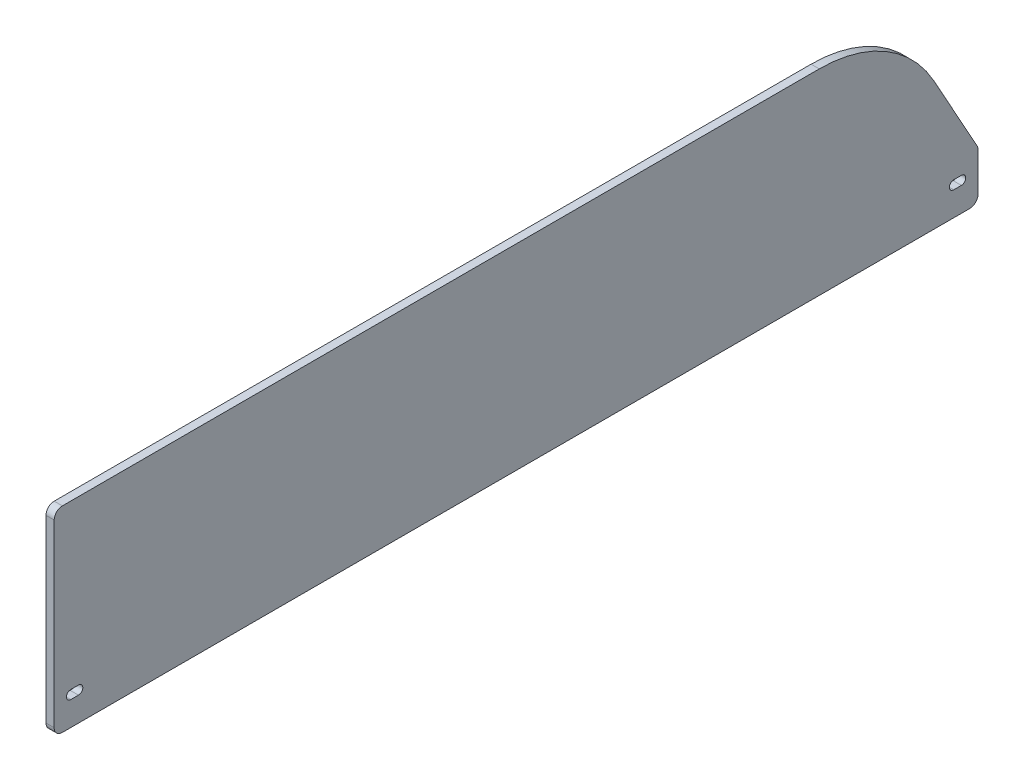
SolidWorks part; units mm, degrees
material "ABS PC"
ref_plane "Front Plane" through (0, 0, 0) normal (0, 0, 1) x (1, 0, 0)
ref_plane "Top Plane" through (0, 0, 0) normal (0, 1, 0) x (1, 0, 0)
ref_plane "Right Plane" through (0, 0, 0) normal (1, 0, 0) x (0, 0, -1)
sketch "Sketch1" plane through (0, 0, 0) normal (1, 0, 0) x (0, 0, -1)
  line L0 (0, 0) -> (0, 152.4)
  line L1 (0, 152.4) -> (654.05, 152.4)
  line L2 (654.05, 152.4) -> (717.55, 38.1)
  line L3 (717.55, 38.1) -> (717.55, 0)
  line L4 (717.55, 0) -> (0, 0)
  dimension "D1" = 38.1
  dimension "D2" = 717.55
  dimension "D3" = 152.4
  dimension "D4" = 63.5
extrude "Boss-Extrude1" add sketch "Sketch1" along normal blind 6.35
fillet "Fillet1" radius 101.6 1 edges at (3.175, 152.4, -654.05)
sketch "Sketch5" plane through (0, 0, 0) normal (-1, 0, 0) x (0, 0, 1)
  line L0 (-717.55, 22.225) -> (0, 22.225) construction
  line L1 (-717.55, 0) -> (-717.55, 38.1) construction
  line L2 (0, 152.4) -> (0, 0) construction
  line L3 (0, 0) -> (-717.55, 0) construction
  point P8 (-701.675, 22.225)
  point P9 (-15.875, 22.225)
  dimension "D1" = 22.225
  dimension "D2" = 15.875
  dimension "D3" = 685.8
hole_wizard "1/4 Clearance Slot1" positions "Sketch6" profile "Sketch7" size "1/4" standard "ANSI Inch" slot yes end condition through all
sketch "Sketch6" plane through (0, 0, 0) normal (-1, 0, 0) x (0, 0, 1)
  line L1 (-22.225, 22.225) -> (-9.525, 22.225) construction
  point P0 (-15.875, 22.225)
  point P7 (-701.675, 22.225)
  dimension "D1" = 12.7
sketch "Sketch7" plane through (0, 22.225, -15.875) normal (0, 1, 0) x (0, 0, 1)
  line L0 (0, 0) -> (0, 6.35)
  line L1 (0, 6.35) -> (3.3782, 6.35)
  line L2 (3.3782, 6.35) -> (3.3782, 0)
  line L5 (3.3782, 0) -> (0, 0)
  line L11 (0, -6.35) -> (0, 107.95) construction
  dimension "Thru Hole Dia." = 6.7564
  dimension "Thru Hole Depth" = 6.35
fillet "Fillet2" radius 6.35 4 edges at (3.175, 38.1, -717.55) (3.175, 0, -717.55) (3.175, 152.4, 0) (3.175, 0, 0)
